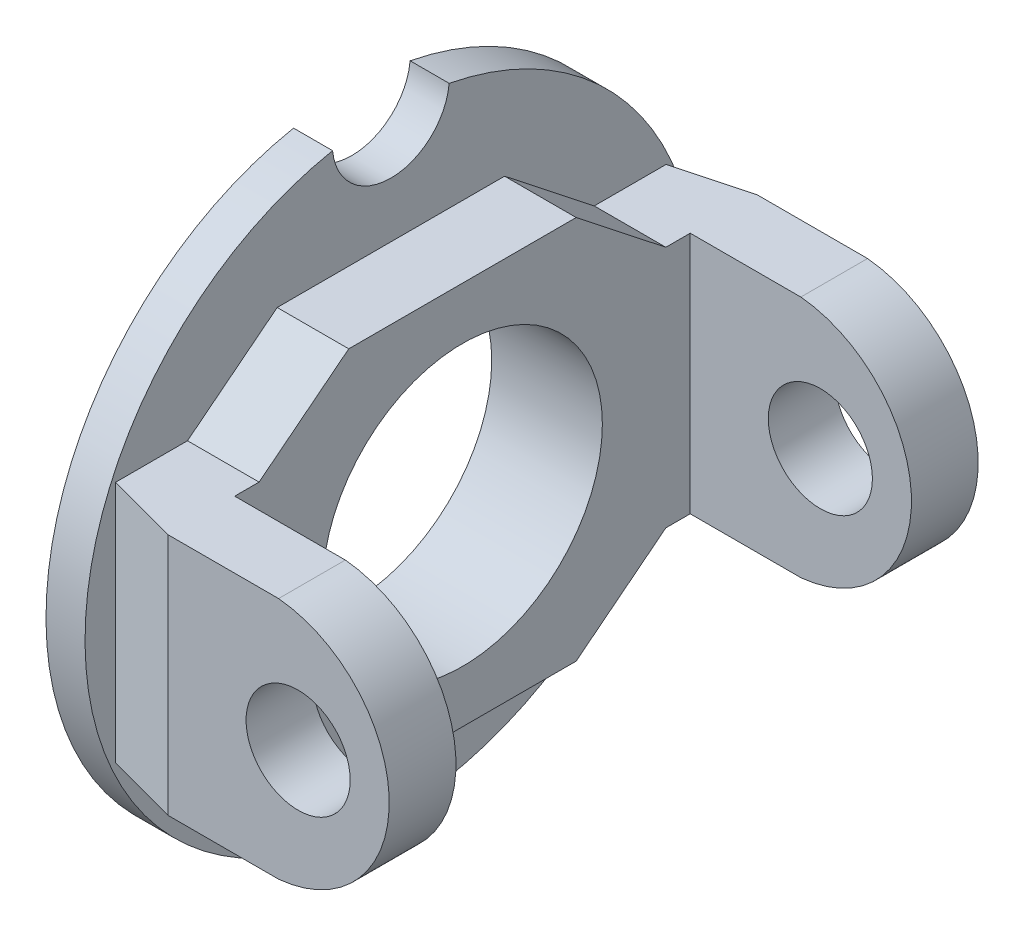
SolidWorks part; units mm, degrees
ref_plane "Ön Düzlem" through (0, 0, 0) normal (0, 0, 1) x (1, 0, 0)
ref_plane "Üst Düzlem" through (0, 0, 0) normal (0, 1, 0) x (1, 0, 0)
ref_plane "Sağ Düzlem" through (0, 0, 0) normal (1, 0, 0) x (0, 0, -1)
sketch "Sketch1" plane through (0, 0, 0) normal (1, 0, 0) x (0, 0, -1)
  line L0 (0, 0) -> (0, 19) construction
  arc A0 (-4.4793, 23.0691) -> (4.4793, 23.0691) centre (0, 0) ccw
  circle A1 centre (0, 0) radius 10.75
  arc A2 (-4.4793, 23.0691) -> (4.4793, 23.0691) centre (0, 23.5) ccw
  dimension "D1" = 47
  dimension "D2" = 21.5
  dimension "D3" = 9
  dimension "D4" = 23.5
extrude "Boss-Extrude1" add sketch "Sketch1" along normal blind 3
sketch "Sketch2" plane through (3, 0, 0) normal (1, 0, 0) x (0, 0, -1)
  line L0 (-15.6269, 9.3372) -> (-8.7368, 14.7601)
  line L1 (-8.7368, 14.7601) -> (8.7368, 14.7601)
  line L2 (8.7368, 14.7601) -> (15.6269, 9.3372)
  line L3 (15.6269, 9.3372) -> (15.6269, -9.3372)
  line L4 (15.6269, -9.3372) -> (8.7368, -14.7601)
  line L5 (8.7368, -14.7601) -> (-8.7368, -14.7601)
  line L6 (-8.7368, -14.7601) -> (-15.6269, -9.3372)
  line L7 (-15.6269, -9.3372) -> (-15.6269, 9.3372)
  line L8 (0, 14.7601) -> (0, -14.7601) construction
  line L9 (-15.6269, 0) -> (15.6269, 0) construction
  line L10 (15.6269, 9.3372) -> (22.6269, 9.3372)
  line L11 (22.6269, 9.3372) -> (22.6269, -9.3372)
  line L12 (22.6269, -9.3372) -> (15.6269, -9.3372)
  line L13 (-22.6269, -9.3372) -> (-15.6269, -9.3372)
  line L14 (-22.6269, 9.3372) -> (-22.6269, -9.3372)
  line L15 (-15.6269, 9.3372) -> (-22.6269, 9.3372)
  circle A0 centre (0, 0) radius 10.75
  point P10 (0, 0)
  point P22 (-15.6269, -9.3378)
  arc M14 (-4.4793, 23.0691) -> (4.4793, 23.0691) centre (0, 0) ccw
  circle M15 centre (0, 0) radius 10.75
  dimension "D1" = 7
extrude "Boss-Extrude2" add sketch "Sketch2" along normal blind 5.5 contours L7 L15 L14 L13 M14 | L7 L6 L5 L4 L3 L2 L1 L0 M15 | L12 L11 L10 L3 M14 | L15 L14 M14 | L14 L13 M14 | L11 L10 M14 | L12 L11 M14 region at (3, 11.7108, 11.916) region at (3, 0, 19.054) region at (3, 8.378, 22.2851) region at (3, -8.378, 22.2851) region at (3, 0, -19.054) region at (3, -8.378, -22.2851) region at (3, 8.378, -22.2851)
draft "Draft5" type of draft neutral plane draft angle 15 faces to draft 2 face at (4.8333, 0, -22.6269) face at (4.8333, 0, 22.6269) neutral plane through (8.5, 0, 0) neutral plane normal (1, 0, 0) reverse direction yes parameters "D1"=15
sketch "Sketch3" plane through (8.5, 0, 0) normal (1, 0, 0) x (0, 0, -1)
  line L0 (-17.5, 9.3372) -> (-22.6269, 9.3372)
  line L1 (-22.6269, 9.3372) -> (-22.6269, -9.3372)
  line L2 (-22.6269, -9.3372) -> (-17.5, -9.3372)
  line L3 (-17.5, -9.3372) -> (-17.5, 9.3372)
  line L4 (17.5, 9.3372) -> (17.5, -9.3372)
  line L5 (17.5, -9.3372) -> (22.6269, -9.3372)
  line L6 (22.6269, -9.3372) -> (22.6269, 9.3372)
  line L7 (22.6269, 9.3372) -> (17.5, 9.3372)
  point P12 (-16.9872, 9.3372)
  dimension "D1" = 35
  dimension "D2" = 17.5
extrude "Boss-Extrude3" add sketch "Sketch3" along normal blind 17
sketch "Sketch4" plane through (0, 0, 22.6269) normal (0, 0, 1) x (1, 0, 0)
  line L0 (25.5, 9.3372) -> (8.5, 9.3372) construction
  line L1 (25.5, -9.3372) -> (8.5, -9.3372) construction
  line L2 (17, 9.3372) -> (17, 12.8808)
  line L3 (17, 12.8808) -> (29.4437, 12.8808)
  line L4 (29.4437, 12.8808) -> (29.4437, -13.0886)
  line L5 (29.4437, -13.0886) -> (17, -13.0886)
  line L6 (17, -13.0886) -> (17, -9.3372)
  arc A0 (17, 9.3372) -> (17, -9.3372) centre (16.1216, 0) cw
extrude "Cut-Extrude1" cut sketch "Sketch4" against normal up to surface (45.2538 mm away) up to face at (17, 0, -22.6269)
sketch "Sketch5" plane through (0, 0, 22.6269) normal (0, 0, 1) x (1, 0, 0)
  line L0 (18.5, 0) -> (25.5, 0) construction
  circle A0 centre (18.5, 0) radius 4
  arc A1 (17, -9.3372) -> (17, 9.3372) centre (16.1216, 0) ccw construction
  dimension "D1" = 8
  dimension "D2" = 7
extrude "Cut-Extrude2" cut sketch "Sketch5" against normal up to surface (45.2538 mm away) up to face at (14.875, 0, -22.6269)
